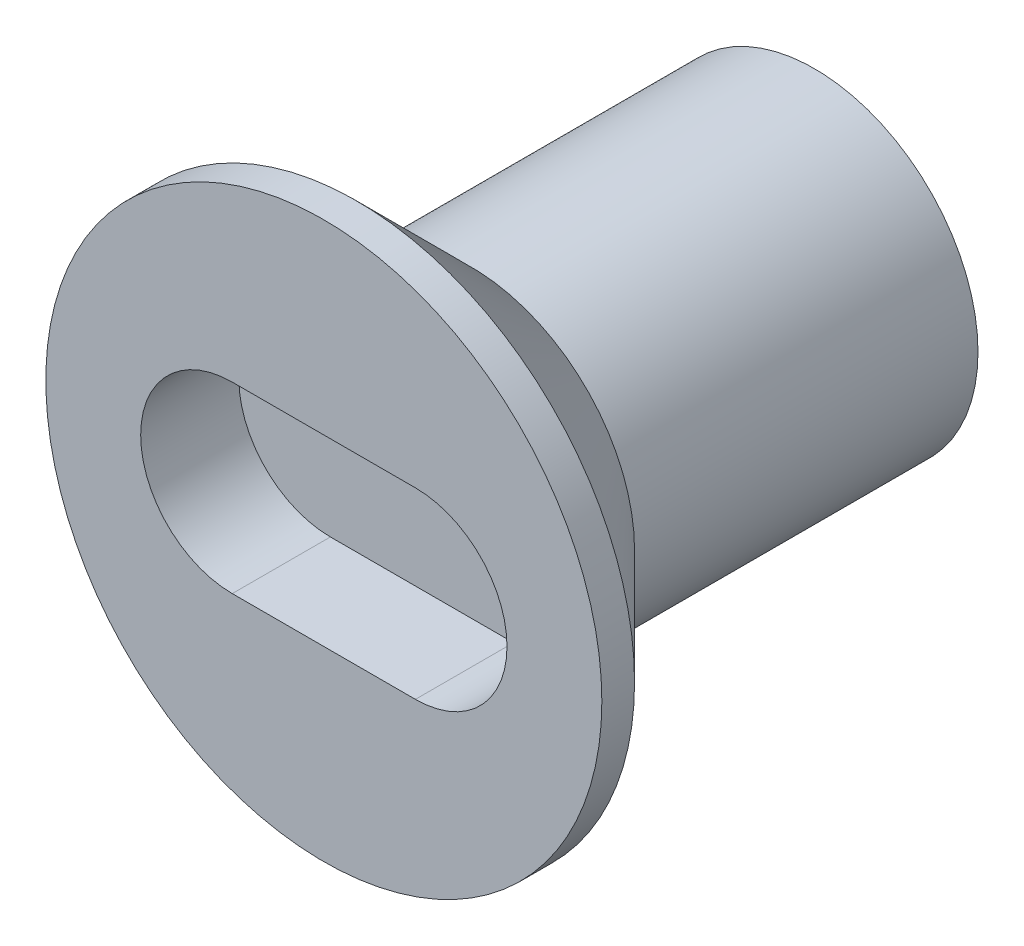
SolidWorks part; units mm, degrees
ref_plane "Front Plane" through (0, 0, 0) normal (0, 0, 1) x (1, 0, 0)
ref_plane "Top Plane" through (0, 0, 0) normal (0, 1, 0) x (1, 0, 0)
ref_plane "Right Plane" through (0, 0, 0) normal (1, 0, 0) x (0, 0, -1)
sketch "Sketch1" plane through (0, 0, 0) normal (0, 0, 1) x (1, 0, 0)
  circle A0 centre (0, 0) radius 5
  dimension "D1" = 10
extrude "Boss-Extrude1" add sketch "Sketch1" along normal blind 10
sketch "Sketch2" plane through (0, 0, 10) normal (0, 0, 1) x (1, 0, 0)
  circle A0 centre (0, 0) radius 8.5
  dimension "D1" = 17
extrude "Boss-Extrude2" add sketch "Sketch2" along normal blind 5
sketch "Sketch3" plane through (0, 0, 15) normal (0, 0, 1) x (1, 0, 0)
  line L0 (0, 0) -> (2.8, 0)
  line L1 (0, 0) -> (-2.8, 0)
  line L2 (-2.8, 2.8) -> (2.8, 2.8)
  line L3 (-2.8, -2.8) -> (2.8, -2.8)
  arc A0 (-2.8, 2.8) -> (-2.8, -2.8) centre (-2.8, 0) ccw
  arc A1 (2.8, -2.8) -> (2.8, 2.8) centre (2.8, 0) ccw
  dimension "D2" = 5.6
  dimension "D3" = 5.6
  dimension "D1" = 2.8
extrude "Cut-Extrude1" cut sketch "Sketch3" against normal blind 3 contours A0 L3 A1 L2
chamfer "Chamfer1" distance 4 angle 45 1 edges at (8.5, 0, 10)
